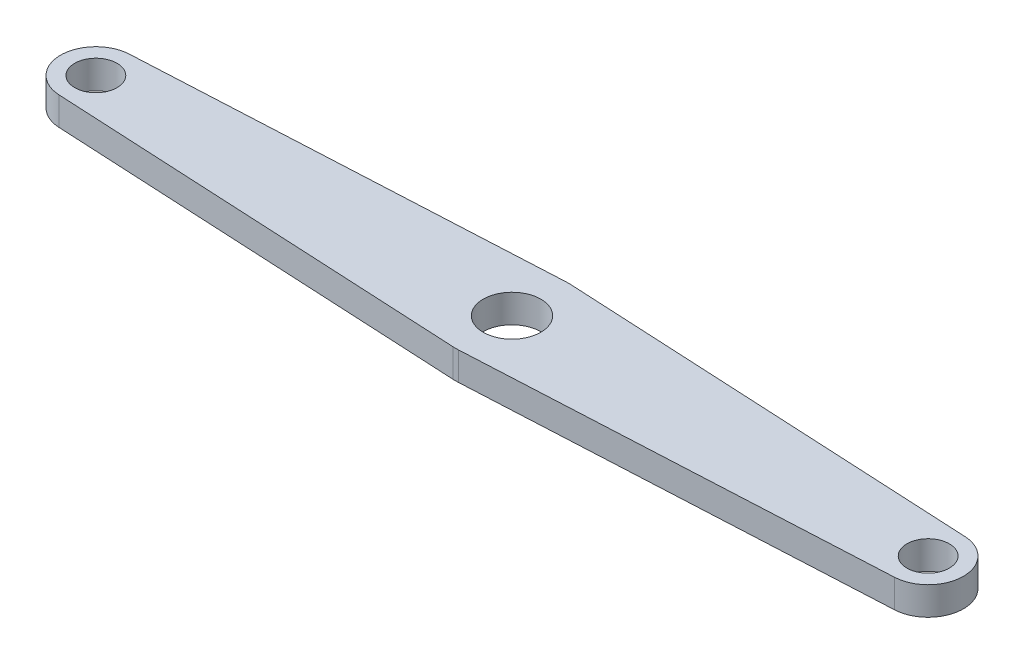
SolidWorks part; units mm, degrees
ref_plane "Alzado" through (0, 0, 0) normal (0, 0, 1) x (1, 0, 0)
ref_plane "Planta" through (0, 0, 0) normal (0, 1, 0) x (1, 0, 0)
ref_plane "Vista lateral" through (0, 0, 0) normal (1, 0, 0) x (0, 0, -1)
sketch "Croquis1" plane through (0, 0, 0) normal (0, 1, 0) x (1, 0, 0)
  line L0 (-147.5, 0) -> (147.5, 0) construction
  line L1 (-148.1356, 12.4838) -> (-1.0169, 19.9741)
  line L2 (-148.1356, -12.4838) -> (-1.0169, -19.9741)
  line L3 (0, 0) -> (0, 42.1122) construction
  line L4 (148.1356, -12.4838) -> (1.0169, -19.9741)
  line L5 (148.1356, 12.4838) -> (1.0169, 19.9741)
  circle A0 centre (0, 0) radius 10.2
  arc A1 (-1.0169, -19.9741) -> (1.0169, -19.9741) centre (0, 0) ccw
  arc A2 (-148.1356, 12.4838) -> (-148.1356, -12.4838) centre (-147.5, 0) ccw
  arc A3 (148.1356, -12.4838) -> (148.1356, 12.4838) centre (147.5, 0) ccw
  arc A4 (1.0169, 19.9741) -> (-1.0169, 19.9741) centre (0, 0) ccw
  point P7 (0, 0)
  dimension "D1" = 20.4
  dimension "D2" = 40
  dimension "D4" = 25
  dimension "D3" = 295
extrude "Saliente-Extruir1" add sketch "Croquis1" along normal mid plane 10
sketch "Croquis3" plane through (0, 0, 0) normal (0, 1, 0) x (1, 0, 0)
  circle A0 centre (-147.5, 0) radius 7.5
  circle A1 centre (147.5, 0) radius 7.5
  dimension "D1" = 15
extrude "Cortar-Extruir2" cut sketch "Croquis3" against normal through all both and the other way through all
